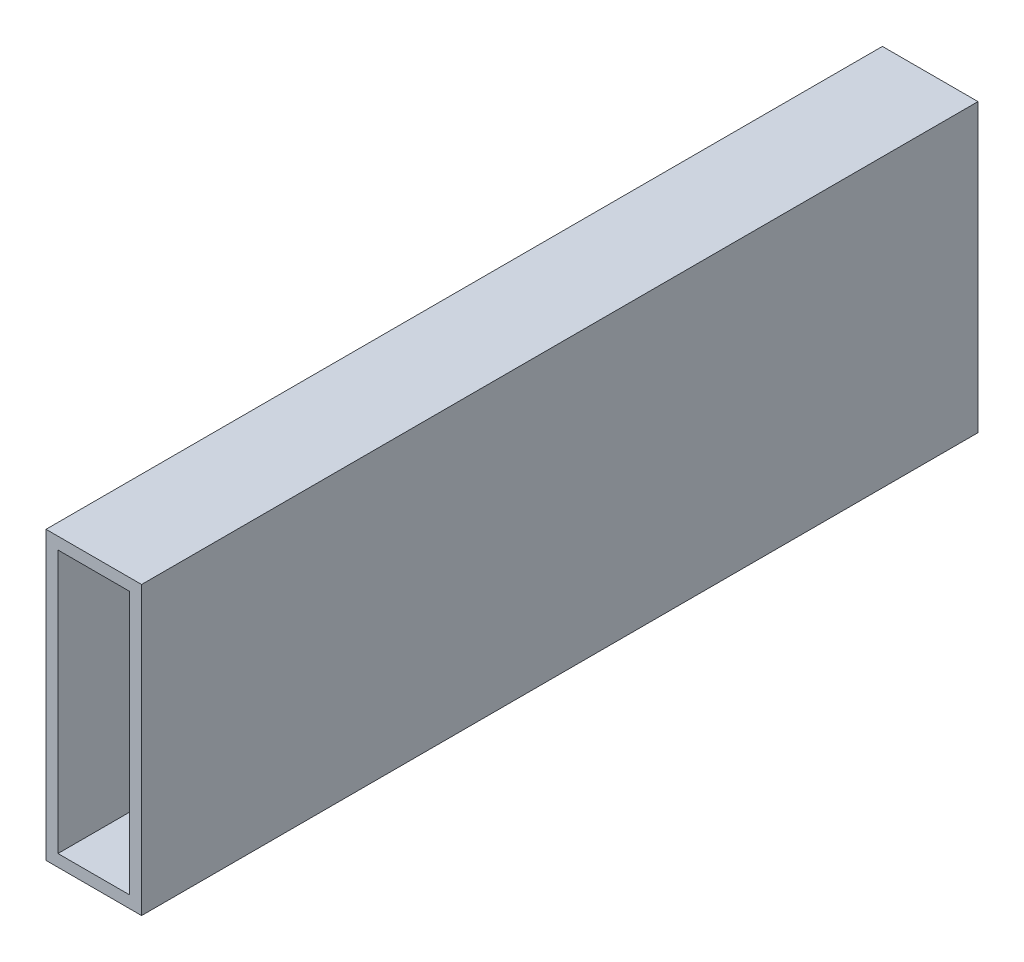
SolidWorks part; units mm, degrees
ref_plane "Front Plane" through (0, 0, 0) normal (0, 0, 1) x (1, 0, 0)
ref_plane "Top Plane" through (0, 0, 0) normal (0, 1, 0) x (1, 0, 0)
ref_plane "Right Plane" through (0, 0, 0) normal (1, 0, 0) x (0, 0, -1)
sketch "Sketch1" plane through (0, 0, 0) normal (0, 0, 1) x (1, 0, 0)
  line L0 (0, 38.1) -> (0, 34.925) construction
  line L1 (-12.7, 38.1) -> (12.7, 38.1)
  line L2 (-12.7, 38.1) -> (-12.7, -38.1)
  line L3 (-12.7, -38.1) -> (12.7, -38.1)
  line L4 (12.7, 38.1) -> (12.7, -38.1)
  line L5 (-12.7, 38.1) -> (12.7, -38.1) construction
  line L6 (-12.7, -38.1) -> (12.7, 38.1) construction
  line L7 (-9.525, 34.925) -> (9.525, 34.925)
  line L8 (-9.525, 34.925) -> (-9.525, -34.925)
  line L9 (-9.525, -34.925) -> (9.525, -34.925)
  line L10 (9.525, 34.925) -> (9.525, -34.925)
  line L11 (9.525, 0) -> (12.7, 0) construction
  line L12 (-9.525, 0) -> (-12.7, 0) construction
  line L13 (0, -34.925) -> (0, -38.1) construction
  point P0 (0, 0)
  dimension "D1" = 76.2
  dimension "D2" = 25.4
  dimension "D3" = 3.175
extrude "Boss-Extrude1" add sketch "Sketch1" along normal blind 222.25
